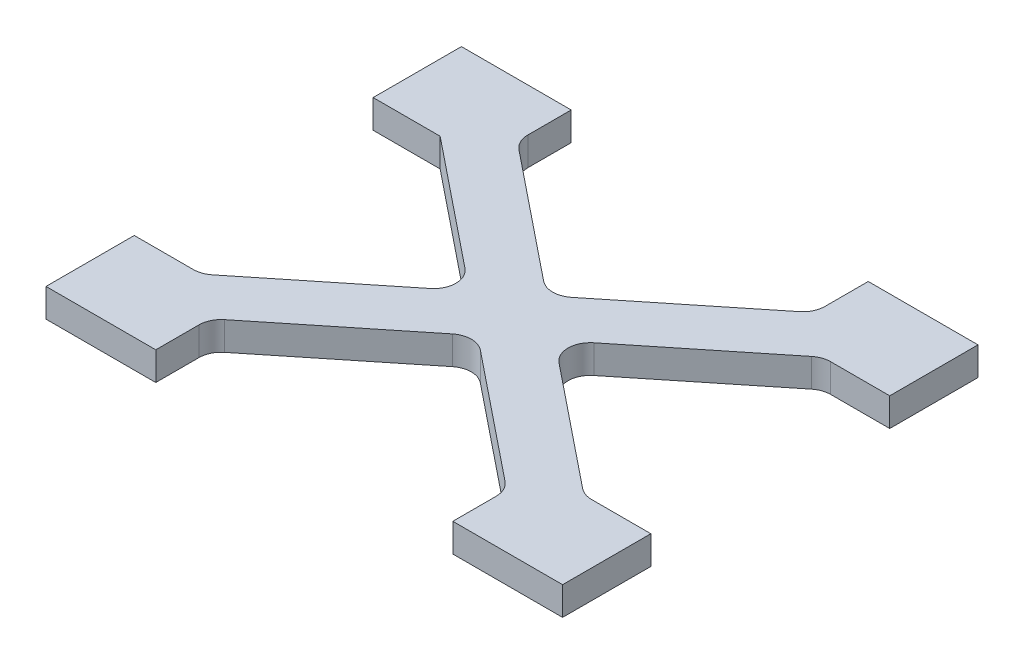
SolidWorks part; units mm, degrees
ref_plane "Front Plane" through (0, 0, 0) normal (0, 0, 1) x (1, 0, 0)
ref_plane "Top Plane" through (0, 0, 0) normal (0, 1, 0) x (1, 0, 0)
ref_plane "Right Plane" through (0, 0, 0) normal (1, 0, 0) x (0, 0, -1)
sketch "Sketch1" plane through (0, 0, 0) normal (0, 1, 0) x (1, 0, 0)
  line L1 (57.825, 46.5) -> (-57.825, 46.5) construction
  line L2 (57.825, 46.5) -> (57.825, -46.5) construction
  line L3 (57.825, -46.5) -> (-57.825, -46.5) construction
  line L4 (-57.825, 46.5) -> (-57.825, -46.5) construction
  line L5 (-57.825, 46.5) -> (57.825, -46.5) construction
  line L6 (-57.825, 26.7384) -> (-42.825, 26.7384)
  line L36 (-42.825, 26.7384) -> (-9.5745, 0)
  line L37 (-9.5745, 0) -> (-42.825, -26.7384)
  line L38 (-42.825, -26.7384) -> (-57.825, -26.7384)
  line L39 (-57.825, -26.7384) -> (-57.825, -46.5)
  line L40 (-57.825, -46.5) -> (-33.2505, -46.5)
  line L41 (-33.2505, -46.5) -> (-33.2505, -34.4377)
  line L42 (-33.2505, -34.4377) -> (0, -7.6993)
  line L43 (0, -7.6993) -> (33.2505, -34.4377)
  line L44 (33.2505, -34.4377) -> (33.2505, -46.5)
  line L45 (33.2505, -46.5) -> (57.825, -46.5)
  line L46 (57.825, -46.5) -> (57.825, -26.7384)
  line L47 (57.825, -26.7384) -> (42.825, -26.7384)
  line L48 (42.825, -26.7384) -> (9.5745, 0)
  line L49 (9.5745, 0) -> (42.825, 26.7384)
  line L50 (42.825, 26.7384) -> (57.825, 26.7384)
  line L51 (57.825, 26.7384) -> (57.825, 46.5)
  line L52 (57.825, 46.5) -> (33.2505, 46.5)
  line L53 (33.2505, 46.5) -> (33.2505, 34.4377)
  line L54 (33.2505, 34.4377) -> (0, 7.6993)
  line L55 (0, 7.6993) -> (-33.2505, 34.4377)
  line L56 (-33.2505, 34.4377) -> (-33.2505, 46.5)
  line L57 (-33.2505, 46.5) -> (-57.825, 46.5)
  line L58 (-57.825, 46.5) -> (-57.825, 26.7384)
  line L59 (-57.825, -46.5) -> (57.825, 46.5) construction
  line L65 (42.825, 26.7384) -> (33.2505, 34.4377) construction
  dimension "D1" = 115.65
  dimension "D2" = 93
  dimension "D3" = 12
  dimension "D4" = 15
extrude "Boss-Extrude1" add sketch "Sketch1" along normal blind 6.35
fillet "Fillet1" radius 5 11 edges at (-33.2505, 3.175, -34.4377) (33.2505, 3.175, -34.4377) (42.825, 3.175, -26.7384) (42.825, 3.175, 26.7384) (33.2505, 3.175, 34.4377) (-33.2505, 3.175, 34.4377) (-42.825, 3.175, 26.7384) (-9.5745, 3.175, 0) (0, 3.175, -7.6993) (9.5745, 3.175, 0) (0, 3.175, 7.6993)
equation "\"L1L\"=500"
equation "\"L1Thick\"=6.35"
equation "\"Harm-Drive-Outer\"=74.5"
equation "\"L1-Spacing\"=115.65"
equation "\"L-Bracket-HoleToWall\"=12.5"
equation "\"L-Bracket-HoleToSide\"=11"
equation "\"Bracket-Hole-D\"=6.8"
equation "\"D1@Sketch1\"=\"L1-Spacing\""
